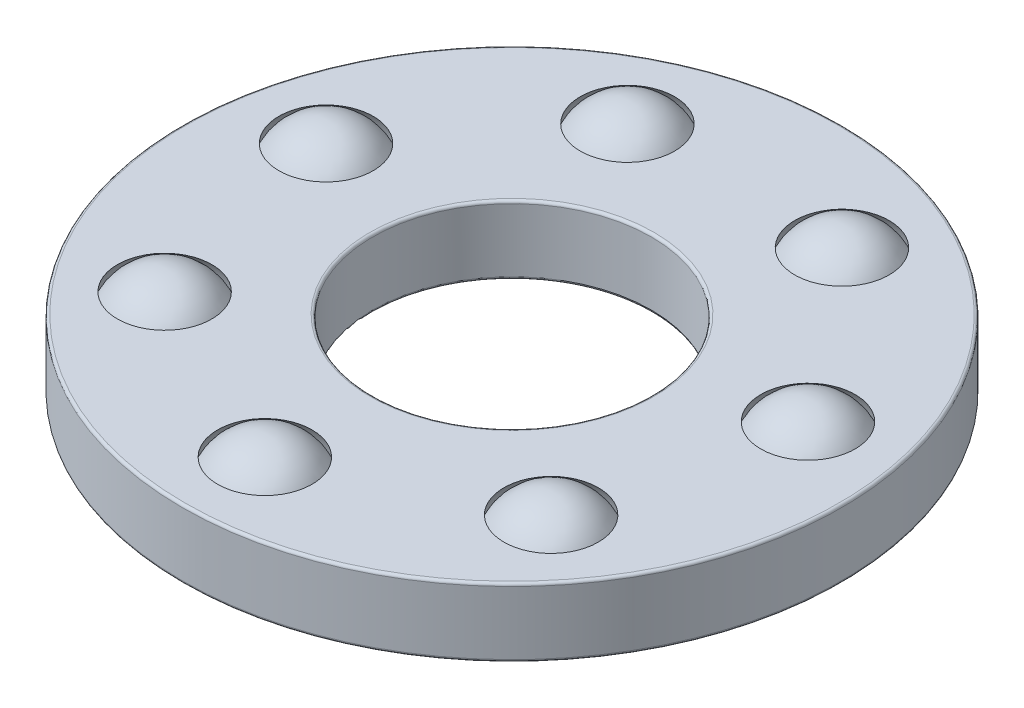
SolidWorks part; units mm, degrees
ref_plane "Front Plane" through (0, 0, 0) normal (0, 0, 1) x (1, 0, 0)
ref_plane "Top Plane" through (0, 0, 0) normal (0, 1, 0) x (1, 0, 0)
ref_plane "Right Plane" through (0, 0, 0) normal (1, 0, 0) x (0, 0, -1)
sketch "Sketch1" plane through (0, 0, 0) normal (1, 0, 0) x (0, 0, -1)
  line L0 (-6, 0) -> (6, 0) construction
  line L1 (0, -2.46) -> (0, 2.46) construction
  line L2 (-6, 0.625) -> (-2.538, 0.625)
  line L3 (-6, 0.625) -> (-6, -0.625)
  line L4 (-6, -0.625) -> (-2.538, -0.625)
  line L5 (-2.538, 0.625) -> (-2.538, -0.625)
  line L6 (-4.5, 1) -> (-4.5, -1) construction
  circle A0 centre (-4.5, 0) radius 1 construction
  dimension "D2" = 1.25
revolve "Revolve1" add sketch "Sketch1" angle 360 about L1
sketch "Sketch3" plane through (0, 0, 0) normal (1, 0, 0) x (0, 0, -1)
  line L0 (-4.5, 1.0625) -> (-4.5, -1.0625)
  line L1 (-4.5, 1) -> (-4.5, -1) construction
  line L2 (-4.4375, 1.0607) -> (-4.4375, -1.0607) construction
  arc A0 (-4.5, 1) -> (-4.5, -1) centre (-4.5, 0) ccw construction
  circle A1 centre (-4.5, 0) radius 1 construction
  arc A2 (-4.5, 1.0625) -> (-4.5, -1.0625) centre (-4.5, 0) ccw
  arc A3 (-4.4375, 1.0607) -> (-4.4375, -1.0607) centre (-4.5, 0) ccw construction
  dimension "D1" = 0.0625
revolve "Cut-Revolve1" cut sketch "Sketch3" angle 360 about L0
sketch "Sketch2" plane through (0, 0, 0) normal (1, 0, 0) x (0, 0, -1)
  line L0 (-4.5, 1) -> (-4.5, -1)
  arc A0 (-4.5, 1) -> (-4.5, -1) centre (-4.5, 0) ccw
  circle A2 centre (-4.5, 0) radius 1 construction
revolve "Revolve2" add sketch "Sketch2" angle 360 about L0
ref_axis "Axis1" through (0, 2.46, 0) along (0, -1, 0)
pattern_circular "CirPattern1" count 7 every 51.429 about axis through (0, 2.46, 0) along (0, -1, 0) of bodies 187
pattern_circular "CirPattern2" count 7 every 51.429 about axis through (0, 2.46, 0) along (0, -1, 0) of "Cut-Revolve1"
sketch "Sketch4" plane through (0, 0, 0) normal (1, 0, 0) x (0, 0, -1)
  line L0 (-6, 0.625) -> (-6, -0.625) construction
  line L1 (-6, 1) -> (-2.538, 1)
  line L2 (-6, 1) -> (-6, 2.46)
  line L3 (-6, 2.46) -> (-2.538, 2.46)
  line L4 (-2.538, 1) -> (-2.538, 2.46)
  line L5 (-6, -2.46) -> (-2.538, -2.46)
  line L6 (-6, -2.46) -> (-6, -1)
  line L7 (-6, -1) -> (-2.538, -1)
  line L8 (-2.538, -2.46) -> (-2.538, -1)
  line L10 (-2.538, 0.625) -> (-2.538, -0.625) construction
  line L11 (0, 0) -> (-6, 0) construction
  line L12 (-6, 0) -> (6, 0) construction
  dimension "Ht" = 4.92
  dimension "Washer Thickness" = 1.46
revolve "Revolve3" add sketch "Sketch4" angle 360 about L1
fillet "Fillet1" radius 0.0492 4 edges at (0, 1, -2.538) (0, 2.46, -2.538) (0, 1, -6) (0, 2.46, -6)
fillet "Fillet2" radius 0.0492 4 edges at (0, -0.625, -2.538) (0, 0.625, -2.538) (0, -0.625, -6) (0, 0.625, -6)
fillet "Fillet3" radius 0.0492 4 edges at (0, -2.46, -2.538) (0, -1, -2.538) (0, -2.46, -6) (0, -1, -6)
delete or keep bodies "Body-Delete/Keep 1" type delete bodies bodies 211 210
ref_plane "Plane1" through (0, -1, 0) normal (0, -1, 0) x (-1, 0, 0)
ref_plane "Plane2" through (0, 1, 0) normal (0, 1, 0) x (1, 0, 0)
equation "\"D2@Sketch1\" = \"Roller Ball Dia@Sketch1\"*.625"
equation "\"Angle@CirPattern1\" = 360/\"Balls@CirPattern1\""
equation "\"D1@CirPattern2\" = \"Balls@CirPattern1\""
equation "\"D2@CirPattern2\" = \"Angle@CirPattern1\""
equation "\"D1@Fillet1\" = \"Th@Sketch1\"*.01"
equation "\"D1@Fillet2\" = \"D1@Fillet1\""
equation "\"D1@Fillet3\" = \"D1@Fillet1\""
